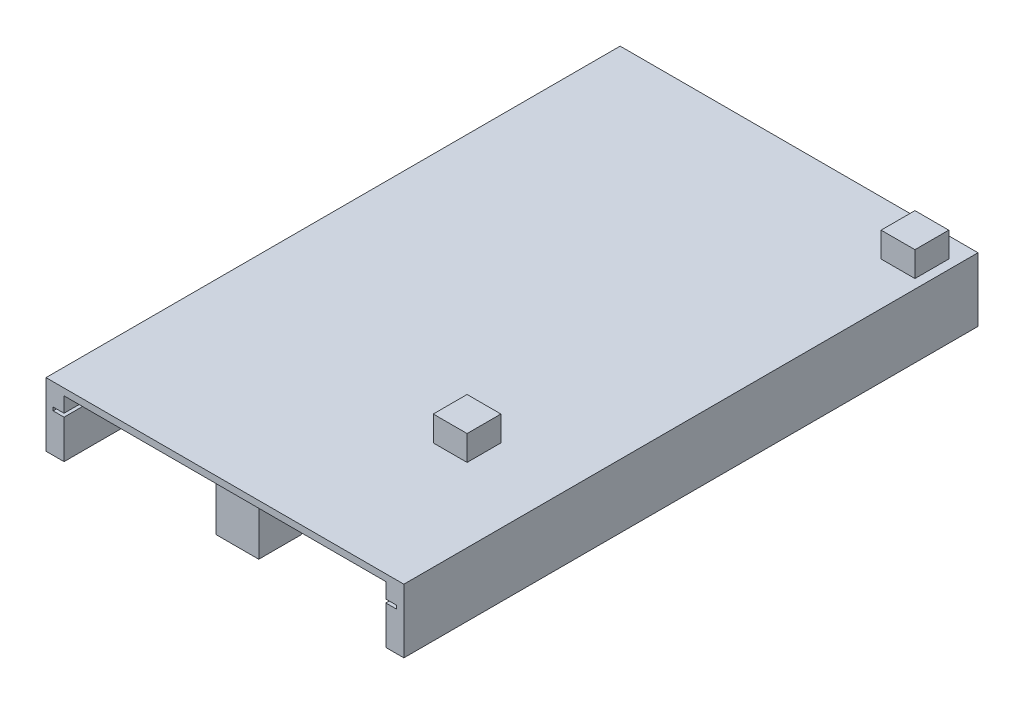
SolidWorks part; units mm, degrees
material "PLA"
ref_plane "Спереди" through (0, 0, 0) normal (0, 0, 1) x (1, 0, 0)
ref_plane "Сверху" through (0, 0, 0) normal (0, 1, 0) x (1, 0, 0)
ref_plane "Справа" through (0, 0, 0) normal (1, 0, 0) x (0, 0, -1)
sketch "Эскиз1" plane through (0, 0, 0) normal (0, 1, 0) x (1, 0, 0)
  line L0 (0, 0) -> (-4740.9496, 0) construction
  line L1 (0, 0) -> (0, -4740.9496) construction
  line L2 (35.675, 63.65) -> (39.675, 63.65)
  line L3 (-35.675, -63.65) -> (-39.675, -63.65)
  line L4 (-35.675, -63.65) -> (-35.675, 63.65)
  line L5 (-35.675, 63.65) -> (-39.675, 63.65)
  line L6 (-39.675, -63.65) -> (-39.675, 63.65)
  line L7 (-35.675, -63.65) -> (-39.675, 63.65) construction
  line L8 (-35.675, 63.65) -> (-39.675, -63.65) construction
  line L9 (39.675, -63.65) -> (39.675, 63.65)
  line L10 (35.675, -63.65) -> (39.675, -63.65)
  line L11 (35.675, -63.65) -> (35.675, 63.65)
  line L12 (35.675, 63.65) -> (39.675, -63.65) construction
  line L13 (35.675, -63.65) -> (39.675, 63.65) construction
  point P5 (-37.675, 0)
  point P14 (37.675, 0)
  dimension "D1" = 4
  dimension "D2" = 127.3
  dimension "D3" = 71.35
extrude "Бобышка-Вытянуть1" add sketch "Эскиз1" along normal blind 12.65
sketch "Эскиз2" plane through (0, 12.65, 0) normal (0, 1, 0) x (1, 0, 0)
  line L1 (39.675, 63.65) -> (-39.675, 63.65)
  line L2 (39.675, 63.65) -> (39.675, -63.65)
  line L3 (39.675, -63.65) -> (-39.675, -63.65)
  line L4 (-39.675, 63.65) -> (-39.675, -63.65)
extrude "Бобышка-Вытянуть2" add sketch "Эскиз2" along normal blind 1.5
sketch "Эскиз3" plane through (0, 0, -63.65) normal (0, 0, -1) x (-1, 0, 0)
  line L0 (0, 0) -> (0, 50000) construction
  line L1 (-35.675, 12.65) -> (-35.675, 0) construction
  line L2 (-35.675, 9.3) -> (-38.075, 9.3)
  line L3 (-35.675, 9.3) -> (-35.675, 8.55)
  line L4 (-35.675, 8.55) -> (-38.075, 8.55)
  line L5 (-38.075, 9.3) -> (-38.075, 8.55)
  line L6 (35.675, 8.55) -> (38.075, 8.55)
  line L7 (38.075, 9.3) -> (38.075, 8.55)
  line L8 (35.675, 9.3) -> (38.075, 9.3)
  line L9 (35.675, 9.3) -> (35.675, 8.55)
  line L10 (-39.675, 0) -> (-35.675, 0) construction
  dimension "D1" = 2.4
  dimension "D2" = 0.75
  dimension "D3" = 8.55
extrude "Вырез-Вытянуть1" cut sketch "Эскиз3" against normal through all from offset 1.5 offset against normal yes
sketch "Эскиз4" plane through (0, 12.65, 0) normal (0, -1, 0) x (1, 0, 0)
  line L0 (35.675, -63.65) -> (35.675, 63.65) construction
  line L1 (-35.675, -63.65) -> (35.675, -63.65)
  line L2 (-35.675, -63.65) -> (-35.675, -62.15)
  line L3 (-35.675, -62.15) -> (35.675, -62.15)
  line L4 (35.675, -63.65) -> (35.675, -62.15)
  dimension "D1" = 1.5
extrude "Бобышка-Вытянуть3" add sketch "Эскиз4" along normal up to surface (12.65 mm away) up to face at (37.675, 0, 0)
sketch "Эскиз6" plane through (0, 12.65, 0) normal (0, -1, 0) x (1, 0, 0)
  line L0 (35.675, -62.15) -> (35.675, 63.65) construction
  line L1 (32.325, -52.35) -> (24.825, -52.35)
  line L2 (32.325, -52.35) -> (32.325, -62.15)
  line L3 (32.325, -59.85) -> (24.825, -59.85) construction
  line L4 (24.825, -52.35) -> (24.825, -62.15)
  line L5 (32.325, -52.35) -> (24.825, -59.85) construction
  line L6 (32.325, -59.85) -> (24.825, -52.35) construction
  line L7 (35.675, -62.15) -> (-35.675, -62.15) construction
  line L8 (32.325, -62.15) -> (24.825, -62.15)
  circle A0 centre (28.575, -56.1) radius 2.1 construction
  point P0 (28.575, -56.1)
  dimension "D3" = 4.2
  dimension "D4" = 1.65
  dimension "D5" = 1.65
  dimension "D1" = 7.1
  dimension "D2" = 6.05
extrude "Бобышка-Вытянуть5" add sketch "Эскиз6" along normal blind 9.6
sketch "Эскиз7" plane through (0, 3.05, 0) normal (0, -1, 0) x (1, 0, 0)
  line L0 (24.825, -52.35) -> (32.325, -59.85) construction
  line L1 (32.325, -52.35) -> (24.825, -59.85) construction
  line L2 (32.325, -62.15) -> (32.325, -52.35) construction
  line L3 (24.825, -52.35) -> (24.825, -62.15) construction
  circle A0 centre (28.575, -56.1) radius 2.05
  dimension "D1" = 4.1
extrude "Вырез-Вытянуть2" cut sketch "Эскиз7" against normal blind 4.5
sketch "Эскиз8" plane through (0, 0, 0) normal (0, -1, 0) x (1, 0, 0)
  line L0 (-35.675, 63.65) -> (-35.675, -62.15) construction
  line L1 (-35.675, 38.05) -> (-38.075, 38.05)
  line L2 (-35.675, 38.05) -> (-35.675, 32.2)
  line L3 (-35.675, 32.2) -> (-38.075, 32.2)
  line L4 (-38.075, 38.05) -> (-38.075, 32.2)
  line L5 (0, 0) -> (0, 50000) construction
  line L6 (-35.675, -16.55) -> (-38.075, -16.55)
  line L7 (-35.675, -16.55) -> (-35.675, -22.4)
  line L8 (-35.675, -22.4) -> (-38.075, -22.4)
  line L9 (-38.075, -16.55) -> (-38.075, -22.4)
  line L10 (-39.675, 63.65) -> (-35.675, 63.65) construction
  line L11 (35.675, -22.4) -> (38.075, -22.4)
  line L12 (38.075, -16.55) -> (38.075, -22.4)
  line L13 (35.675, -16.55) -> (38.075, -16.55)
  line L14 (35.675, -16.55) -> (35.675, -22.4)
  line L15 (35.675, 32.2) -> (38.075, 32.2)
  line L16 (38.075, 38.05) -> (38.075, 32.2)
  line L17 (35.675, 38.05) -> (38.075, 38.05)
  line L18 (35.675, 38.05) -> (35.675, 32.2)
  line L19 (39.675, -63.65) -> (-39.675, -63.65) construction
  point P26 (0, -63.65)
  dimension "D1" = 2.4
  dimension "D2" = 5.85
  dimension "D3" = 48.75
  dimension "D4" = 25.6
extrude "Вырез-Вытянуть3" cut sketch "Эскиз8" against normal up to surface (8.55 mm away) up to face at (-36.875, 8.55, 0.75)
sketch "Эскиз10" plane through (0, 12.65, 0) normal (0, -1, 0) x (1, 0, 0)
  line L0 (-35.675, 63.65) -> (-35.675, -62.15) construction
  line L1 (-25.275, -51.75) -> (-28.275, -51.75)
  line L2 (-25.275, -51.75) -> (-25.275, -57.7)
  line L3 (-25.275, -57.7) -> (-28.275, -57.7)
  line L4 (-28.275, -51.75) -> (-28.275, -57.7)
  line L5 (24.825, -62.15) -> (-35.675, -62.15) construction
  line L6 (35.675, -62.15) -> (-35.675, -62.15) construction
  line L8 (15.225, -51.75) -> (18.225, -51.75)
  line L9 (15.225, -51.75) -> (15.225, -57.7)
  line L10 (15.225, -57.7) -> (18.225, -57.7)
  line L11 (18.225, -51.75) -> (18.225, -57.7)
  dimension "D1" = 10.4
  dimension "D2" = 4.45
  dimension "D3" = 10.4
  dimension "D4" = 3
  dimension "D5" = 50.9
extrude "Бобышка-Вытянуть6" add sketch "Эскиз10" along normal blind 3.95
sketch "Эскиз11" plane through (0, 12.65, 0) normal (0, -1, 0) x (1, 0, 0)
  line L1 (-25.275, -57.7) -> (15.225, -57.7)
  line L2 (-25.275, -57.7) -> (-25.275, -51.75)
  line L3 (-25.275, -51.75) -> (15.225, -51.75)
  line L4 (15.225, -57.7) -> (15.225, -51.75)
extrude "Бобышка-Вытянуть7" add sketch "Эскиз11" along normal blind 0.35
fillet "Скругление4" radius 4 1 edges at (-5.025, 12.65, -57.7)
fillet "Скругление5" radius 2 2 edges at (-26.775, 8.7, -57.7) (16.725, 8.7, -57.7)
sketch "Эскиз12" plane through (0, 0, -62.15) normal (0, 0, 1) x (1, 0, 0)
  line L0 (24.825, 12.65) -> (-35.675, 12.65) construction
  line L1 (15.475, 8) -> (-25.525, 8)
  line L2 (15.475, 8) -> (15.475, 12.65)
  line L12 (15.475, 12.65) -> (-25.525, 12.65)
  line L13 (-25.525, 8) -> (-25.525, 12.65)
  line L15 (-5.025, 12.3) -> (-5.025, 12.65) construction
  line L17 (-25.275, 12.3) -> (15.225, 12.3) construction
  point P13 (-5.025, 12.3)
  dimension "D1" = 4.65
  dimension "D2" = 41
extrude "Вырез-Вытянуть4" cut sketch "Эскиз12" against normal through all
sketch "Эскиз13" plane through (0, 12.65, 0) normal (0, -1, 0) x (1, 0, 0)
  line L0 (0, 63.65) -> (0, 50063.65) construction
  line L1 (-35.675, 63.65) -> (35.675, 63.65) construction
  line L3 (4.75, 60.9) -> (-4.75, 60.9)
  line L4 (4.75, 60.9) -> (4.75, 51.4)
  line L5 (4.75, 51.4) -> (-4.75, 51.4)
  line L6 (-4.75, 60.9) -> (-4.75, 51.4)
  line L7 (4.75, 60.9) -> (-4.75, 51.4) construction
  line L8 (4.75, 51.4) -> (-4.75, 60.9) construction
  circle A0 centre (0, 56.15) radius 2.75 construction
  point P4 (0, 63.65)
  point P5 (0, 56.15)
  dimension "D1" = 5.5
  dimension "D2" = 2
  dimension "D3" = 7.5
extrude "Бобышка-Вытянуть8" add sketch "Эскиз13" along normal blind 12.55
sketch "Эскиз14" plane through (0, 0.1, 0) normal (0, -1, 0) x (1, 0, 0)
  line L0 (-4.75, 60.9) -> (4.75, 51.4) construction
  line L1 (4.75, 60.9) -> (-4.75, 51.4) construction
  circle A0 centre (0, 56.15) radius 1.6
  dimension "D1" = 3.2
extrude "Вырез-Вытянуть5" cut sketch "Эскиз14" against normal blind 7
sketch "Эскиз15" plane through (0, 14.15, 0) normal (0, 1, 0) x (1, 0, 0)
  line L0 (39.675, -63.65) -> (39.675, 63.65) construction
  line L1 (30.1454, 59.1971) -> (37.6454, 59.1971)
  line L2 (30.1454, 59.1971) -> (30.1454, 51.6971)
  line L3 (30.1454, 51.6971) -> (37.6454, 51.6971)
  line L4 (37.6454, 59.1971) -> (37.6454, 51.6971)
  line L5 (30.1454, 59.1971) -> (37.6454, 51.6971) construction
  line L6 (30.1454, 51.6971) -> (37.6454, 59.1971) construction
  line L7 (15.8005, -25.7612) -> (23.3005, -25.7612)
  line L8 (15.8005, -25.7612) -> (15.8005, -33.2612)
  line L9 (15.8005, -33.2612) -> (23.3005, -33.2612)
  line L10 (23.3005, -25.7612) -> (23.3005, -33.2612)
  line L11 (15.8005, -25.7612) -> (23.3005, -33.2612) construction
  line L12 (15.8005, -33.2612) -> (23.3005, -25.7612) construction
  line L13 (-39.675, -63.65) -> (39.675, -63.65) construction
  point P0 (33.8954, 55.4471)
  point P5 (19.5505, -29.5112)
  dimension "D1" = 7.5
  dimension "D2" = 20.1245
  dimension "D3" = 34.1388
  dimension "D4" = 5.7796
  dimension "D5" = 119.0971
extrude "Бобышка-Вытянуть9" add sketch "Эскиз15" along normal blind 5.55
chamfer "Фаска1" distance 0.45 angle 45 1 edges at (0, 0.1, 54.55)
